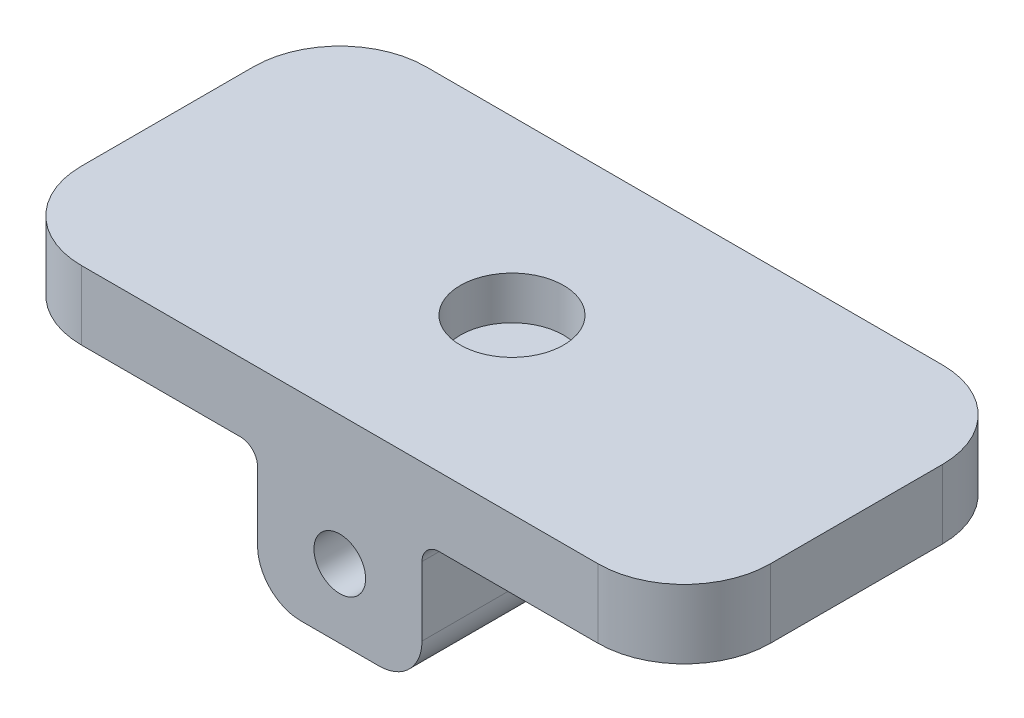
SolidWorks part; units mm, degrees
ref_plane "Front" through (0, 0, 0) normal (0, 0, 1) x (1, 0, 0)
ref_plane "Top" through (0, 0, 0) normal (0, 1, 0) x (1, 0, 0)
ref_plane "Right" through (0, 0, 0) normal (1, 0, 0) x (0, 0, -1)
sketch "Sketch1" plane through (0, 0, 0) normal (0, 0, 1) x (1, 0, 0)
  line L0 (40, 0) -> (-40, 0)
  line L1 (-40, 0) -> (-40, -8)
  line L2 (-40, -8) -> (-9.5455, -8)
  line L3 (40, -8) -> (40, 0)
  line L6 (9.5455, -8) -> (40, -8)
  line L7 (-9.5455, -8) -> (-9.5455, -23)
  line L8 (-9.5455, -23) -> (9.5455, -23)
  line L9 (9.5455, -8) -> (9.5455, -23)
  circle A0 centre (0, -15) radius 3
  point P4 (0, 0)
  point P5 (0, 0)
  point P6 (0, -15)
  point P9 (24.7727, -8)
  point P10 (-15.898, -34.5322)
  point P13 (0, -23)
  dimension "D4" = 6
  dimension "D5" = 8
  dimension "D1" = 80
  dimension "D2" = 8
  dimension "D3" = 15
extrude "Boss-Extrude1" add sketch "Sketch1" along normal blind 40
sketch "Sketch2" plane through (0, 0, 0) normal (0, 0, -1) x (-1, 0, 0)
  line L0 (40, 0) -> (40, -8) construction
  circle A0 centre (32, -4) radius 1.5
  dimension "D1" = 3
  dimension "D2" = 8
extrude "Cut-Extrude1" cut sketch "Sketch2" against normal blind 20
sketch "Sketch6" plane through (0, -23, 0) normal (0, -1, 0) x (1, 0, 0)
  line L1 (-40, 22) -> (40, 22)
  line L2 (-40, 22) -> (-40, 18)
  line L3 (-40, 18) -> (40, 18)
  line L4 (40, 22) -> (40, 18)
  line L5 (0, 18) -> (0, 22) construction
  line L6 (-40, 20) -> (40, 20) construction
  line L7 (40, 40) -> (40, 0) construction
  point P0 (0, 20)
  dimension "D1" = 4
  dimension "D2" = 20
  dimension "D3" = 40
  dimension "D4" = 80
extrude "Cut-Extrude4" cut sketch "Sketch6" against normal up to vertex (15 mm away) up to point (9.5455, -8, 0)
fillet "Fillet1" radius 10 4 edges at (40, -4, 0) (40, -4, 40) (-40, -4, 0) (-40, -4, 40)
fillet "Fillet2" radius 5 4 edges at (9.5455, -23, 31) (9.5455, -23, 9) (-9.5455, -23, 9) (-9.5455, -23, 31)
fillet "Fillet3" radius 2 4 edges at (9.5455, -8, 31) (9.5455, -8, 9) (-9.5455, -8, 31) (-9.5455, -8, 9)
sketch "Sketch7" plane through (0, 0, 0) normal (0, 1, 0) x (1, 0, 0)
  circle A0 centre (0, -20) radius 6
  dimension "D1" = 12
extrude "Cut-Extrude5" cut sketch "Sketch7" against normal blind 5
